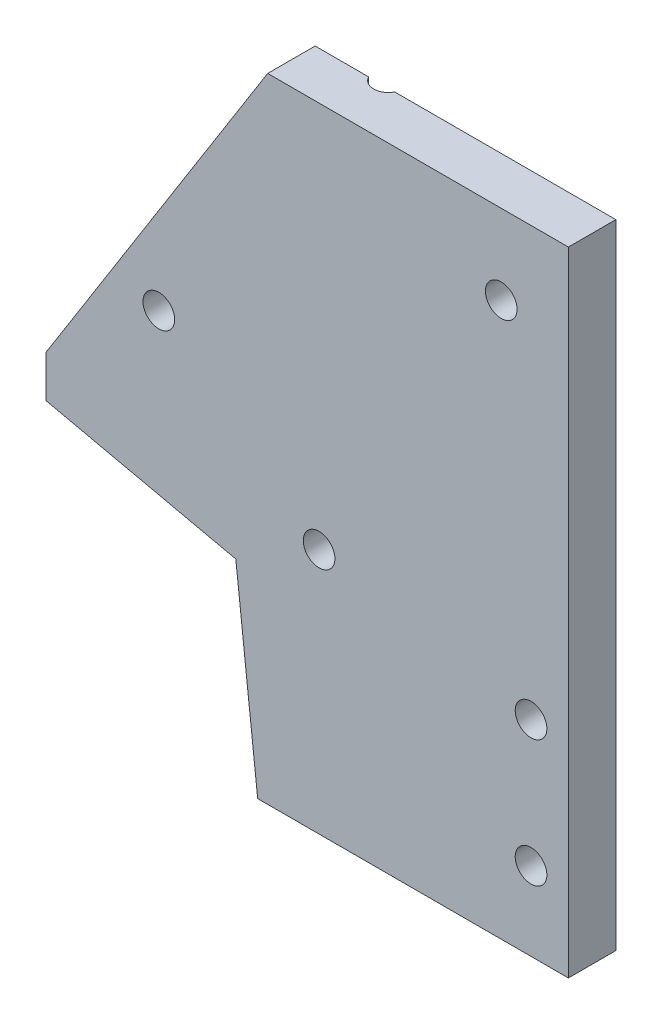
SolidWorks part; units mm, degrees
material "ABS"
ref_plane "Front Plane" through (0, 0, 0) normal (0, 0, 1) x (1, 0, 0)
ref_plane "Top Plane" through (0, 0, 0) normal (0, 1, 0) x (1, 0, 0)
ref_plane "Right Plane" through (0, 0, 0) normal (1, 0, 0) x (0, 0, -1)
sketch "Sketch1" plane through (0, 0, 0) normal (0, 1, 0) x (1, 0, 0)
  line L0 (-18.6025, -15.5102) -> (17.7972, -15.5102)
  line L1 (-41.91, 3.81) -> (41.91, 3.81)
  line L2 (-41.91, 3.81) -> (-41.91, -3.81)
  line L3 (-41.91, -3.81) -> (41.91, -3.81)
  line L4 (41.91, 3.81) -> (41.91, -3.81)
  line L5 (-41.91, 3.81) -> (41.91, -3.81) construction
  line L6 (-41.91, -3.81) -> (41.91, 3.81) construction
  line L7 (-18.6025, 3.81) -> (17.7972, 3.81)
  line L8 (-18.6025, 3.81) -> (-18.6025, 15.5102)
  line L9 (-18.6025, 15.5102) -> (17.7972, 15.5102)
  line L10 (17.7972, 3.81) -> (17.7972, 15.5102)
  line L11 (-18.6025, -15.5102) -> (-18.6025, -3.81)
  line L12 (-18.6025, -3.81) -> (17.7972, -3.81)
  line L13 (17.7972, -15.5102) -> (17.7972, -3.81)
  point P0 (0, 0)
  point P14 (0, 0)
  dimension "D1" = 83.82
  dimension "D2" = 7.62
  dimension "D3" = 11.7002
extrude "Boss-Extrude1" add sketch "Sketch1" along normal blind 101.6 contours L4 L1 L2 L3 region at (0, 0, 0)
extrude "Boss-Extrude2" add sketch "Sketch1<3>" along normal blind 7.62 contours L1 L10 L9 L8 region at (-0.4026, 0, -9.6601)
sketch "Sketch1<3>" plane through (0, 0, 0) normal (0, 1, 0) x (1, 0, 0) same geometry as "Sketch1"
sketch "Sketch2" plane through (0, 0, 3.81) normal (0, 0, 1) x (1, 0, 0)
  line L0 (-41.91, 101.6) -> (-41.91, 0) construction
  line L1 (-41.91, 0) -> (41.91, 0) construction
  line L2 (-41.91, 0) -> (41.91, 0) construction
  line L3 (-23.8252, 59.9016) -> (35.9146, 12.5984) construction
  line L4 (-41.91, 45.0841) -> (-6.3536, 101.6)
  line L5 (-41.91, 101.6) -> (41.91, 101.6) construction
  line L6 (-6.3536, 101.6) -> (-41.91, 101.6)
  line L7 (-41.91, 101.6) -> (-41.91, 45.0841)
  line L8 (-41.91, 38.3216) -> (-11.4666, 31.5429)
  line L9 (-11.4666, 31.5429) -> (-7.9577, 0)
  line L10 (-41.91, 0) -> (41.91, 0) construction
  line L11 (-7.9577, 0) -> (-41.91, 0)
  line L12 (-41.91, 0) -> (-41.91, 38.3216)
  circle A0 centre (-23.8252, 59.9016) radius 2.54
  circle A1 centre (31.1336, 88.819) radius 2.54
  circle A2 centre (1.8961, 39.5349) radius 2.54
  circle A3 centre (35.9146, 12.5984) radius 2.54
  circle A4 centre (35.9146, 32.9184) radius 2.54
  dimension "D8" = 5.08
  dimension "D1" = 18.0848
  dimension "D2" = 59.9016
  dimension "D3" = 62.1022
  dimension "D4" = 88.819
  dimension "D5" = 32.8083
  dimension "D6" = 43.3917
  dimension "D7" = 12.5984
  dimension "D9" = 20.32
extrude "Cut-Extrude1" cut sketch "Sketch2" against normal through all
sketch "Sketch4" plane through (0, 0, 0) normal (0, -1, 0) x (1, 0, 0)
  circle A0 centre (4.3242, -4.8735) radius 2.3424
  circle A1 centre (-1.8016, -9.8729) radius 1.8016
  circle A3 centre (-11.1312, -7.3735) radius 2.035
  circle A4 centre (-14.8016, -10.5428) radius 2.2168
  point P6 (0, 0)
  point P7 (0, 0)
  point P16 (-1.6259, 0.1271)
  point P17 (0, 0)
  point P18 (0, 0)
  point P19 (0, 0)
extrude "Cut-Extrude2" cut sketch "Sketch4" against normal through all
